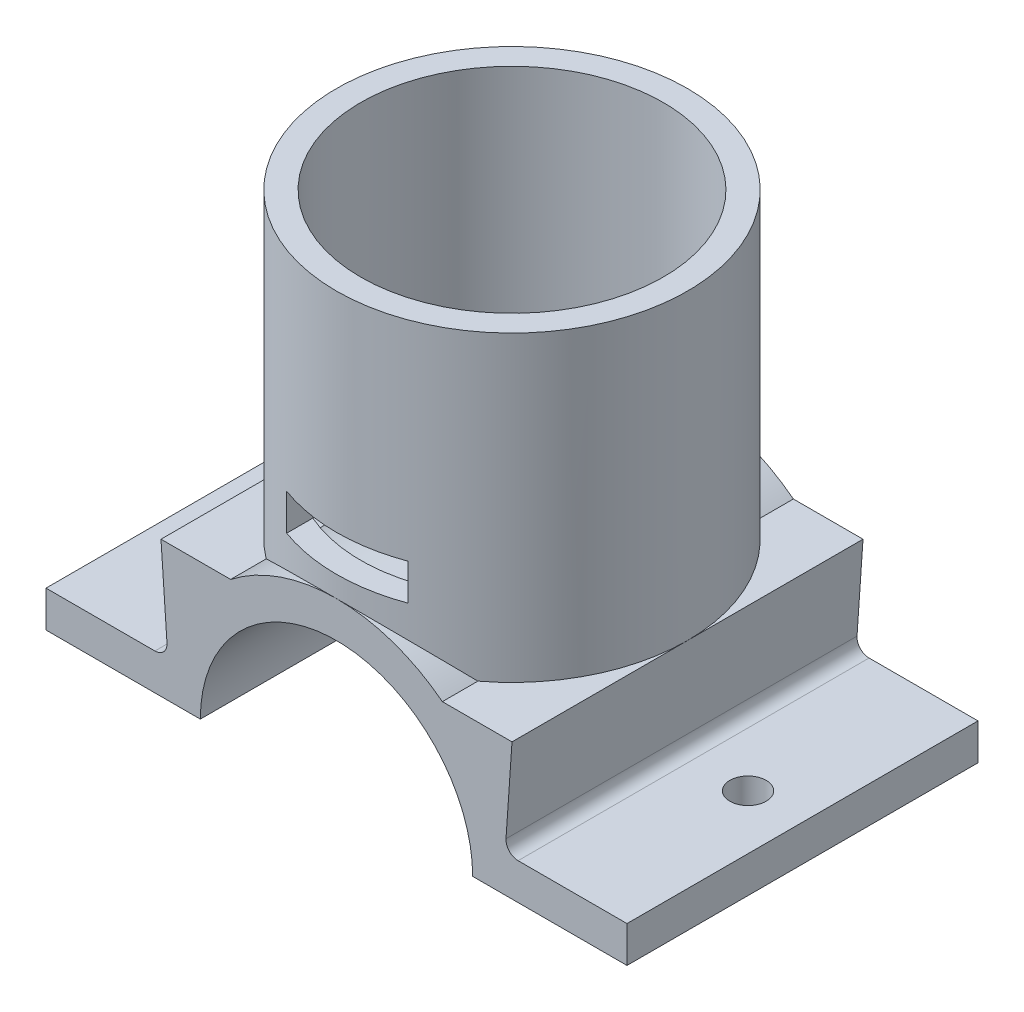
SolidWorks part; units mm, degrees
ref_plane "Front Plane" through (0, 0, 0) normal (0, 0, 1) x (1, 0, 0)
ref_plane "Top Plane" through (0, 0, 0) normal (0, 1, 0) x (1, 0, 0)
ref_plane "Right Plane" through (0, 0, 0) normal (1, 0, 0) x (0, 0, -1)
sketch "Sketch1" plane through (0, 0, 0) normal (0, 1, 0) x (1, 0, 0)
  circle A0 centre (0, 0) radius 12.5
  circle A1 centre (0, 0) radius 14.5
  dimension "D1" = 2
extrude "Boss-Extrude1" add sketch "Sketch1" along normal blind 25
sketch "Sketch2" plane through (0, 0, 0) normal (0, 0, 1) x (1, 0, 0)
  line L0 (-11.25, -11.25) -> (-20, -11.25)
  line L1 (11.25, -11.25) -> (20, -11.25)
  line L2 (15.002, -8.25) -> (20, -8.25)
  line L3 (-15.002, -8.25) -> (-20, -8.25)
  line L6 (-14.0044, -7.1811) -> (-14.5, 0)
  line L7 (-14.5, 0) -> (-8.7464, 0)
  line L8 (14.5, 0) -> (14.0044, -7.1811)
  line L9 (-13.9306, -8.25) -> (-20, -8.25) construction
  line L10 (13.9306, -8.25) -> (20, -8.25) construction
  line L11 (8.7464, 0) -> (14.5, 0)
  line L13 (-24, -11.25) -> (-20, -11.25)
  line L14 (-24, -11.25) -> (-24, -8.25)
  line L15 (-24, -8.25) -> (-20, -8.25)
  line L17 (24, -11.25) -> (20, -11.25)
  line L18 (24, -11.25) -> (24, -8.25)
  line L19 (24, -8.25) -> (20, -8.25)
  arc A0 (11.25, -11.25) -> (-11.25, -11.25) centre (0, -11.25) ccw
  arc A1 (-14.0044, -7.1811) -> (-15.002, -8.25) centre (-15.002, -7.25) cw
  arc A2 (13.9306, -8.25) -> (-13.9306, -8.25) centre (0, -11.25) ccw construction
  arc A3 (15.002, -8.25) -> (14.0044, -7.1811) centre (15.002, -7.25) cw
  arc A4 (8.7464, 0) -> (-8.7464, 0) centre (0, -11.25) ccw
  arc A6 (14.25, -11.25) -> (-14.25, -11.25) centre (0, -11.25) ccw construction
  point P26 (24, -11.25)
  point P27 (-24, -11.25)
  dimension "D1" = 20
  dimension "D3" = 1
  dimension "D2" = 3
  dimension "D5" = 4
  dimension "D6" = 4
  dimension "D4" = 3
extrude "Boss-Extrude2" add sketch "Sketch2" along normal blind 14.5 and the other way blind 14.5
sketch "Sketch3" plane through (0, -11.25, 0) normal (0, -1, 0) x (1, 0, 0)
  circle A0 centre (0, 0) radius 5.9978
extrude "Cut-Extrude1" cut sketch "Sketch3" against normal blind 25
sketch "Sketch4" plane through (0, 0, -14.5) normal (0, 0, -1) x (-1, 0, 0)
  line L0 (-5, 4.7357) -> (-5, 7.7357)
  line L1 (-5, 4.7357) -> (5, 4.7357)
  line L3 (-5, 7.7357) -> (5, 7.7357)
  line L4 (5, 4.7357) -> (5, 7.7357)
  dimension "D1" = 3
extrude "Cut-Extrude2" cut sketch "Sketch4" against normal blind 30
sketch "Sketch6" plane through (0, -8.25, 0) normal (0, 1, 0) x (1, 0, 0)
  circle A0 centre (-19.501, 0) radius 1.5
  circle A1 centre (19.501, 0) radius 1.5
extrude "Cut-Extrude4" cut sketch "Sketch6" against normal blind 30
